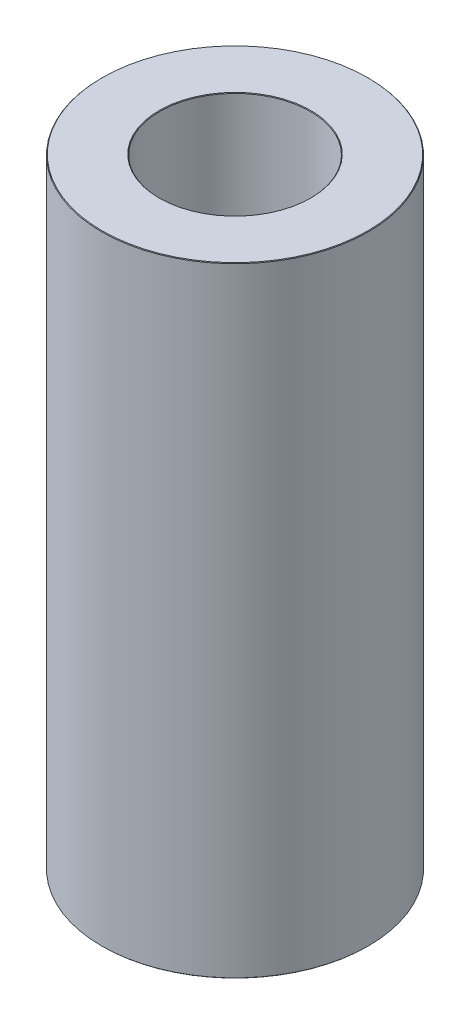
SolidWorks part; units mm, degrees
ref_plane "Front Plane" through (0, 0, 0) normal (0, 0, 1) x (1, 0, 0)
ref_plane "Top Plane" through (0, 0, 0) normal (0, 1, 0) x (1, 0, 0)
ref_plane "Right Plane" through (0, 0, 0) normal (1, 0, 0) x (0, 0, -1)
sketch "Sketch1" plane through (0, 0, 0) normal (0, 1, 0) x (1, 0, 0)
  circle A0 centre (0, 0) radius 55
  dimension "SLEEVE_OD" = 110
extrude "Boss-Extrude1" add sketch "Sketch1" along normal blind 255.6706
sketch "Sketch2" plane through (0, 0, 0) normal (0, 1, 0) x (1, 0, 0)
  circle A0 centre (0, 0) radius 31.0739
  dimension "BORE_D" = 62.1477
extrude "Cut-Extrude1" cut sketch "Sketch2" along normal through all
chamfer "Chamfer1" distance 0.2283 angle 45 4 edges at (0, 255.6706, 31.0739) (0, 0, 31.0739) (0, 0, 55) (0, 255.6706, 55)
